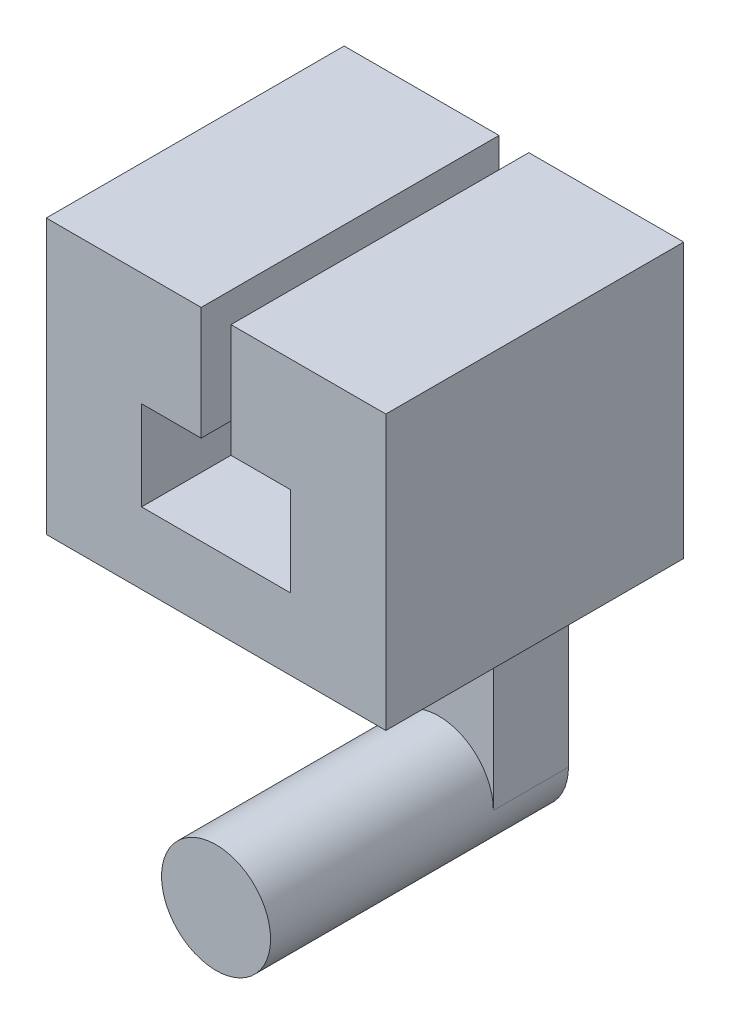
SolidWorks part; units mm, degrees
ref_plane "Front Plane" through (0, 0, 0) normal (0, 0, 1) x (1, 0, 0)
ref_plane "Top Plane" through (0, 0, 0) normal (0, 1, 0) x (1, 0, 0)
ref_plane "Right Plane" through (0, 0, 0) normal (1, 0, 0) x (0, 0, -1)
sketch "Sketch1" plane through (0, 0, 0) normal (0, 0, 1) x (1, 0, 0)
  circle A0 centre (0, 0) radius 23.241
  dimension "D1" = 46.482
extrude "ftA" add sketch "Sketch1" against normal blind 127 contours A0
sketch "Sketch2" plane through (0, 0, -127) normal (0, 0, -1) x (-1, 0, 0)
  line L1 (-23.241, 0) -> (23.241, 0)
  line L2 (-23.241, 0) -> (-23.241, 101.6)
  line L3 (-23.241, 101.6) -> (23.241, 101.6)
  line L4 (23.241, 0) -> (23.241, 101.6)
  circle A0 centre (0, 0) radius 23.241 construction
  dimension "D1" = 46.482
  dimension "D2" = 101.6
extrude "ftB" add sketch "Sketch2" against normal blind 32.004 separate body
sketch "Sketch3" plane through (0, 0, -127) normal (0, 0, -1) x (-1, 0, 0)
  line L0 (-23.241, 101.6) -> (-31.75, 101.6)
  line L9 (-31.75, 101.6) -> (-31.75, 132.08)
  line L10 (-31.75, 132.08) -> (31.75, 132.08)
  line L11 (31.75, 132.08) -> (31.75, 101.6)
  line L12 (31.75, 101.6) -> (23.241, 101.6)
  line L13 (23.241, 101.6) -> (-23.241, 101.6)
  dimension "D1" = 63.5
  dimension "D2" = 30.48
extrude "ftC" add sketch "Sketch3" against normal blind 127 contours L13 L0 L9 L10 L11 L12
sketch "Sketch4" plane through (0, 0, 0) normal (0, 0, 1) x (1, 0, 0)
  line L9 (-31.75, 132.08) -> (-72.39, 132.08)
  line L10 (-31.75, 132.08) -> (-31.75, 170.18)
  line L11 (-31.75, 170.18) -> (-72.39, 170.18)
  line L12 (-72.39, 132.08) -> (-72.39, 170.18)
  line L13 (31.75, 132.08) -> (72.39, 132.08)
  line L14 (31.75, 132.08) -> (31.75, 170.18)
  line L15 (31.75, 170.18) -> (72.39, 170.18)
  line L16 (72.39, 132.08) -> (72.39, 170.18)
  dimension "D1" = 40.64
  dimension "D2" = 38.1
extrude "ftD1" add sketch "Sketch4" against normal blind 127 separate body contours L15 L16 L13 L14
extrude "ftD2" add sketch "Sketch4<5>" against normal blind 127
sketch "Sketch4<5>" plane through (0, 0, 0) normal (0, 0, 1) x (1, 0, 0) same geometry as "Sketch4"
sketch "Sketch5" plane through (0, 0, 0) normal (0, 0, 1) x (1, 0, 0)
  line L1 (-31.75, 170.18) -> (-6.35, 170.18)
  line L2 (-31.75, 170.18) -> (-31.75, 218.44)
  line L3 (-31.75, 218.44) -> (-6.35, 218.44)
  line L4 (-6.35, 170.18) -> (-6.35, 218.44)
  line L5 (31.75, 170.18) -> (6.35, 170.18)
  line L6 (31.75, 170.18) -> (31.75, 218.44)
  line L7 (31.75, 218.44) -> (6.35, 218.44)
  line L8 (6.35, 170.18) -> (6.35, 218.44)
  dimension "D1" = 48.26
  dimension "D2" = 25.4
extrude "ftE" add sketch "Sketch5" against normal blind 127 separate body
sketch "Sketch6" plane through (0, 0, 0) normal (0, 0, 1) x (1, 0, 0)
  line L0 (-31.75, 101.6) -> (31.75, 101.6) construction
  line L5 (31.75, 218.44) -> (72.39, 218.44)
  line L6 (31.75, 218.44) -> (31.75, 170.18)
  line L7 (31.75, 170.18) -> (72.39, 170.18)
  line L8 (72.39, 218.44) -> (72.39, 170.18)
  line L13 (-31.75, 218.44) -> (-72.39, 218.44)
  line L14 (-31.75, 218.44) -> (-31.75, 170.18)
  line L15 (-31.75, 170.18) -> (-72.39, 170.18)
  line L16 (-72.39, 218.44) -> (-72.39, 170.18)
  line L17 (-72.39, 132.08) -> (-31.75, 132.08)
  line L18 (-72.39, 132.08) -> (-72.39, 101.6)
  line L19 (-72.39, 101.6) -> (-31.75, 101.6)
  line L20 (-31.75, 132.08) -> (-31.75, 101.6)
  line L21 (31.75, 101.6) -> (72.39, 101.6)
  line L22 (31.75, 101.6) -> (31.75, 132.08)
  line L23 (31.75, 132.08) -> (72.39, 132.08)
  line L24 (72.39, 101.6) -> (72.39, 132.08)
extrude "Filler" add sketch "Sketch6" against normal blind 127
equation "\"F\"= 600'Applied force"
equation "\"Yst\"= 39885.32'Yield strength"
equation "\"Sf\"= 4'Safety factor"
equation "\"def\"= .005'Deflection"
equation "\"Lst\"= 5'Length of strap"
equation "\"E\"= 10007604'Modulus of elasticity"
equation "\"Dst\"= ( ( \"F\" * \"Lst\" * \"Sf\" * 32 * 2 ) / ( \"Yst\" * 3.14159 ) ) ^ ( 1 / 3 )'Driven diameter of feauture A"
equation "\"Lftb\"= 4'Chosen length of feature B"
equation "\"hftb\"= ( ( \"F\" * \"Lftb\" * \"Sf\" * 6 * 2 ) / ( \"Dst\" * \"Yst\" ) ) ^ ( 1 / 2 )'Driven height of feature B"
equation "\"Bftc\"= 2.5'Base of feature C, from T-beam dim"
equation "\"hftc\"= ( ( \"F\" * \"Lst\" * \"Sf\" * 2 * 6 ) / ( \"Bftc\" * \"Yst\" ) ) ^ ( 1 / 2 )'Driven height of feature C"
equation "\"hftd\"= 1.5'Chosen height of feature D"
equation "\"cftd\"= \"hftd\" / 2'Neutral axis of feature D (distance)"
equation "\"bftd\"= ( \"F\" * \"Lst\" * \"cftd\" * \"Sf\" * 2 * 12 ) / ( \"Yst\" * ( \"hftd\" ^ 3 ) )'Driven base of feature D"
equation "\"bfte\"= 1'Base of feature E, from T-beam dim"
equation "\"hfte\"= ( ( \"F\" * \"Lst\" * \"Sf\" * 6 * 2 ) / ( \"Yst\" * \"bfte\" ) ) ^ ( 1 / 2 )'Driven height of feature E"
equation "\"hlink\"= 6'Chosen height of link"
equation "\"blink\"= 2.25'Chosen base of link"
equation "\"clink\"= 3'Neutral axis of link (distance)"
equation "\"tlink\"= ( \"F\" * \"hlink\" * \"clink\" * \"Sf\" * 12 * 2 ) / ( \"Yst\" * ( \"hlink\" ^ 3 ) )'Driven thickness of link"
